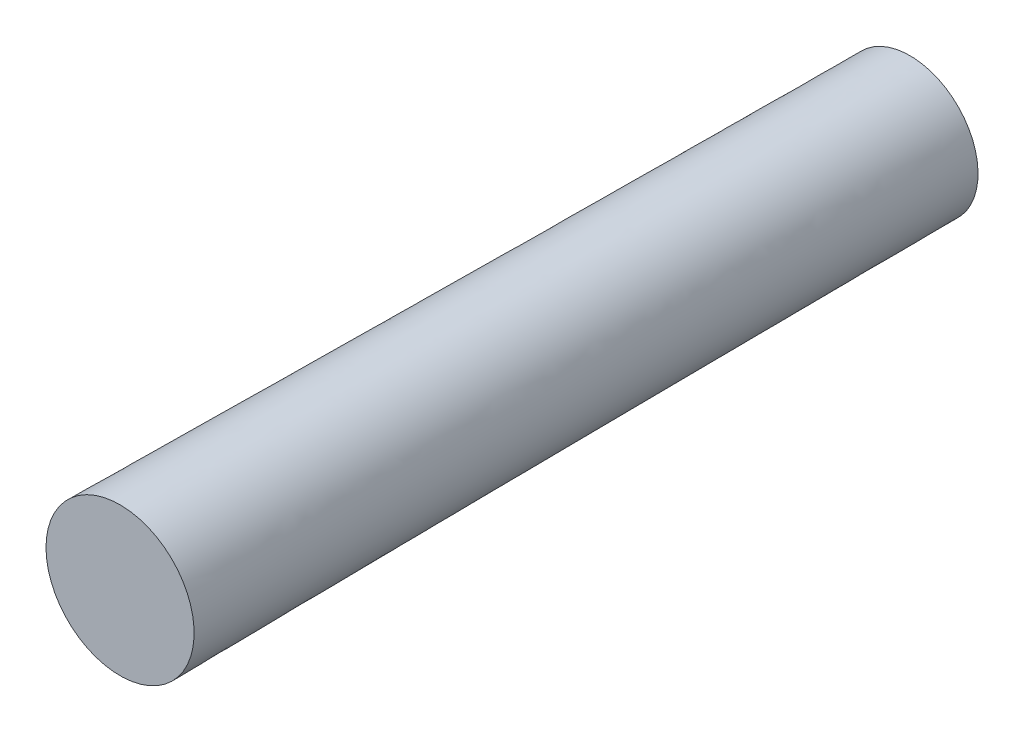
SolidWorks part; units mm, degrees
ref_plane "Front Plane" through (0, 0, 0) normal (0, 0, 1) x (1, 0, 0)
ref_plane "Top Plane" through (0, 0, 0) normal (0, 1, 0) x (1, 0, 0)
ref_plane "Right Plane" through (0, 0, 0) normal (1, 0, 0) x (0, 0, -1)
sketch "Sketch1" plane through (0, 0, 0) normal (0, 0, 1) x (1, 0, 0)
  circle A0 centre (0, 0) radius 8.763
  dimension "D1" = 17.526
ref_plane "Plane1" through (0, 0, 101.6) normal (0, 0, 1) x (1, 0, 0)
sketch "Sketch2" plane through (0, 0, 101.6) normal (0, 0, 1) x (1, 0, 0)
  circle A0 centre (0, 0) radius 9.525
  dimension "D1" = 19.05
loft "Loft1" add profiles "Sketch2", "Sketch1" connector at (-9.5249, -0.0479, 101.6) connector at (-8.4317, 2.3866, 0)
